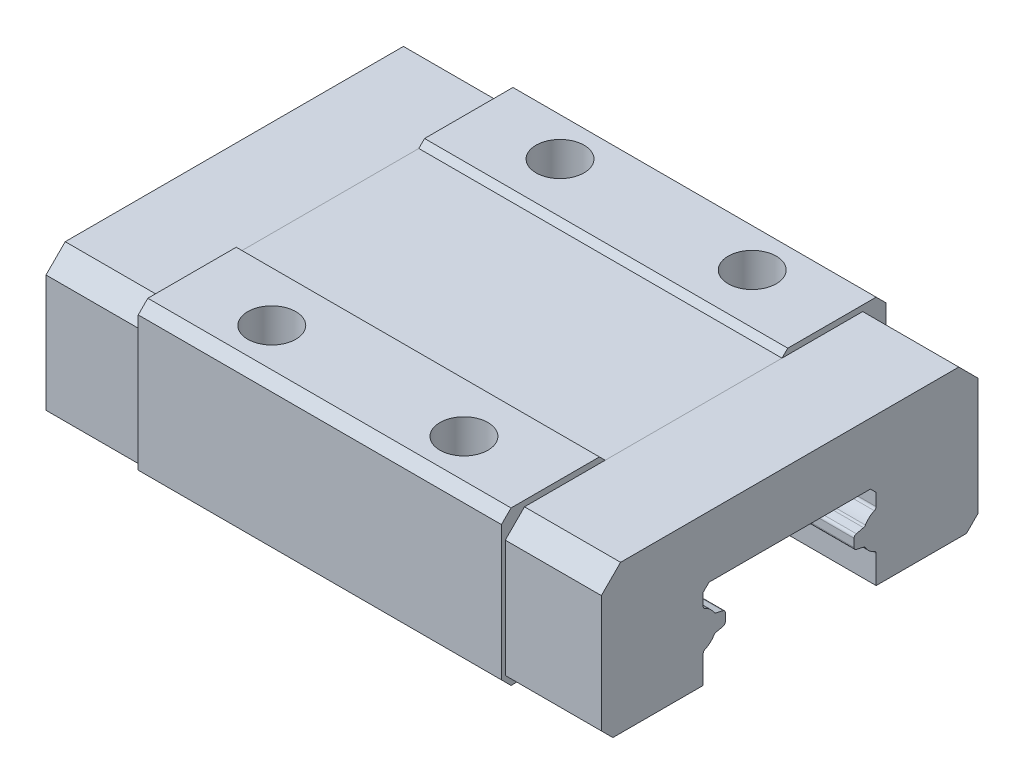
SolidWorks part; units mm, degrees
ref_plane "前视基准面" through (0, 0, 0) normal (0, 0, 1) x (1, 0, 0)
ref_plane "上视基准面" through (0, 0, 0) normal (0, 1, 0) x (1, 0, 0)
ref_plane "右视基准面" through (0, 0, 0) normal (1, 0, 0) x (0, 0, -1)
ref_plane "基准面4" through (0, 0, 0) normal (1, 0, 0) x (0, 0, -1)
sketch "草图1" plane through (0, 0, 0) normal (1, 0, 0) x (0, 0, -1)
  line L0 (-10, 7.5) -> (-10, 0.5)
  line L1 (-10, 0.5) -> (-9.5, 0)
  line L2 (-9.5, 0) -> (9.5, 0)
  line L3 (9.5, 0) -> (10, 0.5)
  line L4 (10, 0.5) -> (10, 7.5)
  line L5 (10, 7.5) -> (9.5, 8)
  line L6 (9.5, 8) -> (4.9, 8)
  line L7 (4.9, 8) -> (4.6, 7.7)
  line L8 (4.6, 7.7) -> (-4.6, 7.7)
  line L9 (-4.6, 7.7) -> (-4.9, 8)
  line L10 (-4.9, 8) -> (-9.5, 8)
  line L11 (-9.5, 8) -> (-10, 7.5)
extrude "凸台-拉伸1" add sketch "草图1" against normal blind 9.45 and the other way blind 9.45
ref_plane "基准面5" through (0, 0, 0) normal (1, 0, 0) x (0, 0, -1)
sketch "草图2" plane through (0, 0, 0) normal (1, 0, 0) x (0, 0, -1)
  line L0 (-9.8, 6.7) -> (-9.8, 0.6)
  line L1 (-9.8, 0.6) -> (-9.2, 0)
  line L2 (-9.2, 0) -> (9.2, 0)
  line L3 (9.2, 0) -> (9.8, 0.6)
  line L4 (9.8, 0.6) -> (9.8, 6.7)
  line L5 (9.8, 6.7) -> (8.8, 7.7)
  line L6 (8.8, 7.7) -> (-8.8, 7.7)
  line L7 (-8.8, 7.7) -> (-9.8, 6.7)
extrude "凸台-拉伸2" add sketch "草图2" against normal blind 14.45 and the other way blind 14.45
ref_plane "基准面6" through (0, 0, 0) normal (1, 0, 0) x (0, 0, -1)
sketch "草图3" plane through (0, 0, 0) normal (1, 0, 0) x (0, 0, -1)
  line L0 (-4.5, 4.2) -> (-4.5, 3.5583)
  line L1 (-3.8438, 2.9397) -> (-3.4666, 2.8536)
  line L2 (-3.35, 2.7074) -> (-3.35, 2.2926)
  line L3 (-3.4666, 2.1464) -> (-3.8438, 2.0603)
  line L4 (-4.5, 1.4417) -> (-4.5, -1.5)
  line L5 (-4.5, -1.5) -> (-4, -2)
  line L6 (-4, -2) -> (1.4, -2)
  line L7 (2.2, -2) -> (4, -2)
  line L8 (4, -2) -> (4.5, -1.5)
  line L9 (4.5, -1.5) -> (4.5, 1.4417)
  line L10 (3.8438, 2.0603) -> (3.4666, 2.1464)
  line L11 (3.35, 2.2926) -> (3.35, 2.7074)
  line L12 (3.4666, 2.8536) -> (3.8438, 2.9397)
  line L13 (4.5, 3.5583) -> (4.5, 4.2)
  line L14 (4.5, 4.2) -> (4.2, 4.5)
  line L15 (4.2, 4.5) -> (-4.2, 4.5)
  line L16 (-4.2, 4.5) -> (-4.5, 4.2)
  arc A0 (-4.5, 3.5583) -> (-4.4084, 3.4201) centre (-4.35, 3.5583) ccw
  arc A1 (-4.4084, 3.4201) -> (-3.9395, 3.0095) centre (-4.8, 2.5) cw
  arc A2 (-3.9395, 3.0095) -> (-3.8438, 2.9397) centre (-3.8104, 3.0859) ccw
  arc A3 (-3.4666, 2.8536) -> (-3.35, 2.7074) centre (-3.5, 2.7074) cw
  arc A4 (-3.35, 2.2926) -> (-3.4666, 2.1464) centre (-3.5, 2.2926) cw
  arc A5 (-3.8438, 2.0603) -> (-3.9395, 1.9905) centre (-3.8104, 1.9141) ccw
  arc A6 (-3.9395, 1.9905) -> (-4.4084, 1.5799) centre (-4.8, 2.5) cw
  arc A7 (-4.4084, 1.5799) -> (-4.5, 1.4417) centre (-4.35, 1.4417) ccw
  arc A8 (1.4, -2) -> (2.2, -2) centre (1.8, -2.3) cw
  arc A9 (4.5, 1.4417) -> (4.4084, 1.5799) centre (4.35, 1.4417) ccw
  arc A10 (4.4084, 1.5799) -> (3.9395, 1.9905) centre (4.8, 2.5) cw
  arc A11 (3.9395, 1.9905) -> (3.8438, 2.0603) centre (3.8104, 1.9141) ccw
  arc A12 (3.4666, 2.1464) -> (3.35, 2.2926) centre (3.5, 2.2926) cw
  arc A13 (3.35, 2.7074) -> (3.4666, 2.8536) centre (3.5, 2.7074) cw
  arc A14 (3.8438, 2.9397) -> (3.9395, 3.0095) centre (3.8104, 3.0859) ccw
  arc A15 (3.9395, 3.0095) -> (4.4084, 3.4201) centre (4.8, 2.5) cw
  arc A16 (4.4084, 3.4201) -> (4.5, 3.5583) centre (4.35, 3.5583) ccw
extrude "切除-拉伸1" cut sketch "草图3" against normal blind 26.45 and the other way blind 24.45
ref_plane "基准面7" through (9.45, 0, 0) normal (1, 0, 0) x (0, 0, -1)
sketch "草图4" plane through (9.45, 0, 0) normal (1, 0, 0) x (0, 0, -1)
  line L0 (-4.5, 4.2) -> (-4.5, 3.5583)
  line L1 (-3.8438, 2.9397) -> (-3.4666, 2.8536)
  line L2 (-3.35, 2.7074) -> (-3.35, 2.2926)
  line L3 (-3.4666, 2.1464) -> (-3.8438, 2.0603)
  line L4 (-4.5, 1.4417) -> (-4.5, -1.5)
  line L5 (-4.5, -1.5) -> (-4, -2)
  line L6 (-4, -2) -> (1.4, -2)
  line L7 (2.2, -2) -> (4, -2)
  line L8 (4, -2) -> (4.5, -1.5)
  line L9 (4.5, -1.5) -> (4.5, 1.4417)
  line L10 (3.8438, 2.0603) -> (3.4666, 2.1464)
  line L11 (3.35, 2.2926) -> (3.35, 2.7074)
  line L12 (3.4666, 2.8536) -> (3.8438, 2.9397)
  line L13 (4.5, 3.5583) -> (4.5, 4.2)
  line L14 (4.5, 4.2) -> (4.2, 4.5)
  line L15 (4.2, 4.5) -> (-4.2, 4.5)
  line L16 (-4.2, 4.5) -> (-4.5, 4.2)
  arc A0 (-4.5, 3.5583) -> (-4.4084, 3.4201) centre (-4.35, 3.5583) ccw
  arc A1 (-4.4084, 3.4201) -> (-3.9395, 3.0095) centre (-4.8, 2.5) cw
  arc A2 (-3.9395, 3.0095) -> (-3.8438, 2.9397) centre (-3.8104, 3.0859) ccw
  arc A3 (-3.4666, 2.8536) -> (-3.35, 2.7074) centre (-3.5, 2.7074) cw
  arc A4 (-3.35, 2.2926) -> (-3.4666, 2.1464) centre (-3.5, 2.2926) cw
  arc A5 (-3.8438, 2.0603) -> (-3.9395, 1.9905) centre (-3.8104, 1.9141) ccw
  arc A6 (-3.9395, 1.9905) -> (-4.4084, 1.5799) centre (-4.8, 2.5) cw
  arc A7 (-4.4084, 1.5799) -> (-4.5, 1.4417) centre (-4.35, 1.4417) ccw
  arc A8 (1.4, -2) -> (2.2, -2) centre (1.8, -2.3) cw
  arc A9 (4.5, 1.4417) -> (4.4084, 1.5799) centre (4.35, 1.4417) ccw
  arc A10 (4.4084, 1.5799) -> (3.9395, 1.9905) centre (4.8, 2.5) cw
  arc A11 (3.9395, 1.9905) -> (3.8438, 2.0603) centre (3.8104, 1.9141) ccw
  arc A12 (3.4666, 2.1464) -> (3.35, 2.2926) centre (3.5, 2.2926) cw
  arc A13 (3.35, 2.7074) -> (3.4666, 2.8536) centre (3.5, 2.7074) cw
  arc A14 (3.8438, 2.9397) -> (3.9395, 3.0095) centre (3.8104, 3.0859) ccw
  arc A15 (3.9395, 3.0095) -> (4.4084, 3.4201) centre (4.8, 2.5) cw
  arc A16 (4.4084, 3.4201) -> (4.5, 3.5583) centre (4.35, 3.5583) ccw
ref_plane "基准面11" through (0, 0, -7.5) normal (0, 0, 1) x (1, 0, 0)
ref_plane "基准面15" through (0, 0, 5) normal (0, 0, 1) x (1, 0, 0)
sketch "草图12" plane through (0, 0, 5) normal (0, 0, 1) x (1, 0, 0)
  line L0 (-13.45, 6.2) -> (-13.45, 7)
  line L1 (-13.45, 7) -> (-13.2605, 6.8105)
  line L2 (-13.2605, 6.8105) -> (-9.45, 6.8105)
  line L3 (-9.45, 6.8105) -> (-9.0975, 6.2)
  line L4 (-9.0975, 6.2) -> (-13.45, 6.2)
  line L5 (-9.0975, 6.2) -> (-13.45, 6.2) construction
revolve "切除-旋转6" cut sketch "草图12" angle 360 about L5 reverse direction yes
ref_plane "基准面16" through (0, 0, 5) normal (0, 0, 1) x (1, 0, 0)
ref_plane "基准面17" through (0, 0, -5) normal (0, 0, 1) x (1, 0, 0)
sketch "草图17" plane through (0, 7.7, 0) normal (0, 1, 0) x (1, 0, 0)
  line L0 (-9.45, 8.8) -> (-9.45, -8.8)
  line L1 (9.45, -8.8) -> (9.45, 8.8)
split line "分割线1"
hole_wizard "M3 螺纹孔1" positions "草图19" profile "草图18" tap size "M3" standard "Gb"
sketch "草图19" plane through (0, 8, 0) normal (0, 1, 0) x (1, 0, 0)
  line L0 (16.8759, 0) -> (-18.6749, 0) construction
  line L1 (0, -9.5) -> (0, 9.5) construction
  line L2 (9.45, -9.5) -> (-9.45, -9.5) construction
  line L3 (9.45, 9.5) -> (-9.45, 9.5) construction
  point P0 (5, -7.5)
  point P2 (-5, -7.5)
  point P4 (5, 7.5)
  point P6 (-5, 7.5)
  dimension "D1" = 10
  dimension "D2" = 10
  dimension "D3" = 15
  dimension "D4" = 15
sketch "草图18" plane through (5, 8, 7.5) normal (1, 0, 0) x (0, 0, 1)
  line L0 (0, 0) -> (0, 7.2511)
  line L1 (0, 7.2511) -> (1.25, 6.5)
  line L2 (1.25, 6.5) -> (1.25, 0)
  line L5 (1.25, 0) -> (0, 0)
  line L10 (0, 7.2511) -> (-1.25, 6.5) construction
  line L11 (0, -6.35) -> (0, 107.95) construction
  dimension "螺纹孔钻头直径" = 2.5
  dimension "螺纹孔钻头深度" = 6.5
  dimension "导头角度" = 118
cosmetic thread "孔螺蚊线1" parameters "D1"=4, "D2"=3
cosmetic thread "孔螺蚊线2" parameters "D1"=4, "D2"=3
cosmetic thread "孔螺蚊线3" parameters "D1"=4, "D2"=3
cosmetic thread "孔螺蚊线4" parameters "D1"=4, "D2"=3
